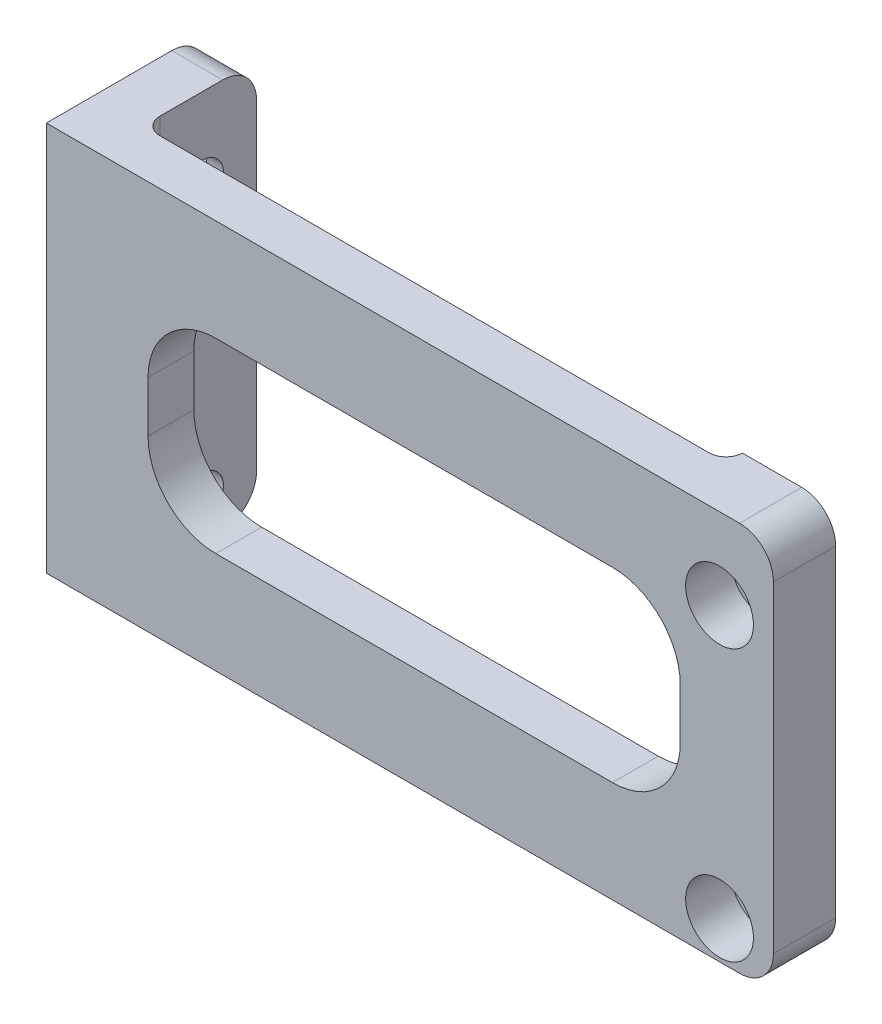
SolidWorks part; units mm, degrees
ref_plane "Front Plane" through (0, 0, 0) normal (0, 0, 1) x (1, 0, 0)
ref_plane "Top Plane" through (0, 0, 0) normal (0, 1, 0) x (1, 0, 0)
ref_plane "Right Plane" through (0, 0, 0) normal (1, 0, 0) x (0, 0, -1)
sketch "Sketch1" plane through (0, 0, 0) normal (0, 0, 1) x (1, 0, 0)
  line L0 (-15.45, 11.5) -> (-15.45, 5.5) construction
  line L1 (21.45, 11.5) -> (-21.45, 11.5)
  line L2 (21.45, 11.5) -> (21.45, -11.5)
  line L3 (21.45, -11.5) -> (-21.45, -11.5)
  line L4 (-21.45, 11.5) -> (-21.45, -11.5)
  line L5 (21.45, 11.5) -> (-21.45, -11.5) construction
  line L6 (21.45, -11.5) -> (-21.45, 11.5) construction
  line L7 (-21.45, 11.5) -> (-18.45, 11.5)
  line L8 (-21.45, 11.5) -> (-21.45, -11.5)
  line L9 (-21.45, -11.5) -> (-18.45, -11.5)
  line L10 (-18.45, 11.5) -> (-18.45, -11.5)
  line L11 (21.45, 11.5) -> (15.95, 11.5)
  line L12 (21.45, 11.5) -> (21.45, -11.5)
  line L13 (21.45, -11.5) -> (15.95, -11.5)
  line L14 (15.95, 11.5) -> (15.95, -11.5)
  line L15 (-15.45, 5.5) -> (15.95, 5.5)
  line L16 (-15.45, 5.5) -> (-15.45, -5.5)
  line L17 (-15.45, -5.5) -> (15.95, -5.5)
  line L18 (15.95, 5.5) -> (15.95, -5.5)
  line L19 (-15.45, 5.5) -> (-21.45, 5.5) construction
  line L20 (-15.45, -5.5) -> (-15.45, -11.5) construction
  circle A0 centre (18.27, -9.28) radius 1.1
  circle A1 centre (18.27, 6.72) radius 1.1
  point P0 (0, 0)
  dimension "D1" = 2.2
  dimension "D2" = 4.78
  dimension "D3" = 23
  dimension "D4" = 2.22
  dimension "D5" = 5.5
  dimension "D6" = 2.32
  dimension "D7" = 42.9
  dimension "D8" = 3
  dimension "D9" = 11
extrude "Boss-Extrude1" add sketch "Sketch1" against normal blind 2.7 contours L14 L1 L10 L3 region at (15.5362, 8.5, 0)
extrude "Boss-Extrude2" add sketch "Sketch1<3>" against normal blind 3.67 contours L1 L14 L3 L2 A1 A0 region at (18.7275, 0.0818, 0)
sketch "Sketch1<3>" plane through (0, 0, 0) normal (0, 0, 1) x (1, 0, 0) same geometry as "Sketch1"
extrude "Boss-Extrude3" add sketch "Sketch1<4>" against normal blind 9.4 contours L10 L1 L4 L3 region at (-19.95, 0, 0)
sketch "Sketch1<4>" plane through (0, 0, 0) normal (0, 0, 1) x (1, 0, 0) same geometry as "Sketch1"
sketch "Sketch2" plane through (-21.45, 0, 0) normal (-1, 0, 0) x (0, 0, 1)
  line L0 (-9.4, 11.5) -> (0, 11.5) construction
  line L1 (0, 11.5) -> (0, -11.5) construction
  circle A0 centre (-6.2, 6.75) radius 1.25
  dimension "D1" = 2.5
  dimension "D2" = 4.75
  dimension "D3" = 6.2
extrude "Cut-Extrude1" cut sketch "Sketch2" against normal up to surface (3 mm away) up to face at (-18.45, 0, -4.7)
pattern_linear "LPattern1" count 2 spacing 16 along (0, -1, 0) of "Cut-Extrude1"
sketch "Sketch3" plane through (-21.45, 0, 0) normal (-1, 0, 0) x (0, 0, 1)
  circle A0 centre (-6.2, 6.75) radius 2
  circle A1 centre (-6.2, -9.25) radius 2
  dimension "D1" = 4
extrude "Cut-Extrude2" cut sketch "Sketch3" against normal offset from surface (2 mm away) 1 up to face at (-18.45, -10.5, -6.2)
sketch "Sketch4" plane through (0, 0, 0) normal (0, 0, 1) x (1, 0, 0)
  circle A0 centre (18.27, 6.72) radius 2
  circle A1 centre (18.27, -9.28) radius 2
  dimension "D1" = 4
extrude "Cut-Extrude3" cut sketch "Sketch4" against normal offset from surface (2.67 mm away) 1 up to face at (19.37, 6.72, -3.67)
combine bodies "Combine1" operation type add bodies to combine 106 107
fillet "Fillet1" radius 2 4 edges at (21.45, -11.5, -1.835) (21.45, 11.5, -1.835) (-19.95, -11.5, -9.4) (-19.95, 11.5, -9.4)
fillet "Fillet2" radius 1 3 edges at (-18.45, 0, -2.7) (15.95, -8.5, -2.7) (15.95, 8.5, -2.7)
fillet "Fillet3" radius 4 4 edges at (15.95, -5.5, -1.835) (15.95, 5.5, -1.835) (-15.45, 5.5, -1.35) (-15.45, -5.5, -1.35)
move or copy body "Corpo-Mover/Copiar1" [suppressed] bodies to move or copy 108
